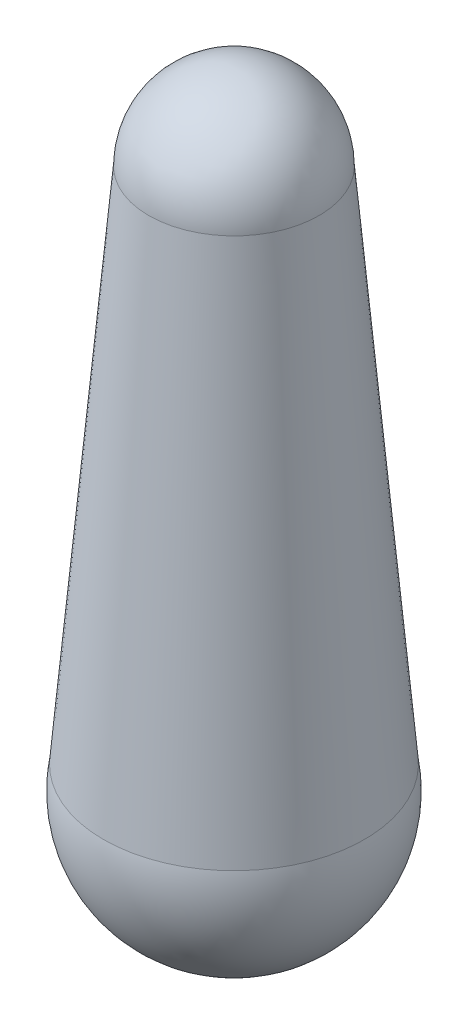
SolidWorks part; units mm, degrees
ref_plane "Front Plane" through (0, 0, 0) normal (0, 0, 1) x (1, 0, 0)
ref_plane "Top Plane" through (0, 0, 0) normal (0, 1, 0) x (1, 0, 0)
ref_plane "Right Plane" through (0, 0, 0) normal (1, 0, 0) x (0, 0, -1)
sketch "Sketch1" plane through (0, 0, 0) normal (0, 1, 0) x (1, 0, 0)
  line L0 (0, 2.45) -> (0, -2.45) construction
  line L1 (0, 2.45) -> (0, -2.45)
  arc A0 (0, -2.45) -> (0, 2.45) centre (0, 0) ccw
  dimension "D1" = 4.9
revolve "Revolve1" add sketch "Sketch1" angle 360 about L0
sketch "Sketch2" plane through (0, 0, 0) normal (0, 1, 0) x (1, 0, 0)
  circle A0 centre (0, 0) radius 2.45
  dimension "D1" = 4.9
extrude "Boss-Extrude1" add sketch "Sketch2" along normal blind 10 draft 5
sketch "Sketch3" plane through (0, 10, 0) normal (0, 1, 0) x (1, 0, 0)
  line L0 (0, 1.5751) -> (0, -1.5751) construction
  line L1 (0, 1.5751) -> (0, -1.5751)
  arc A0 (0, -1.5751) -> (0, 1.5751) centre (0, 0) ccw
  circle A1 centre (0, 0) radius 1.5751 construction
revolve "Revolve2" add sketch "Sketch3" angle 360 about L0
